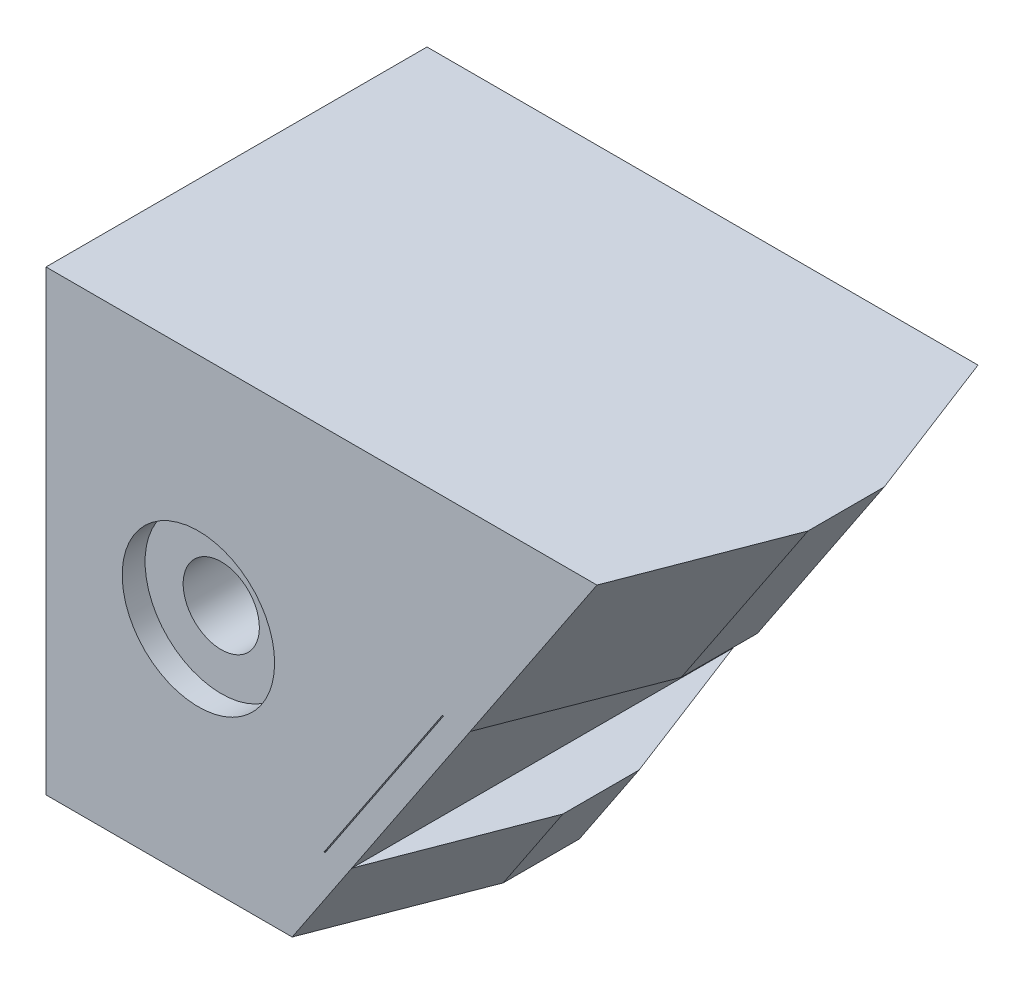
SolidWorks part; units mm, degrees
ref_plane "Front Plane" through (0, 0, 0) normal (0, 0, 1) x (1, 0, 0)
ref_plane "Top Plane" through (0, 0, 0) normal (0, 1, 0) x (1, 0, 0)
ref_plane "Right Plane" through (0, 0, 0) normal (1, 0, 0) x (0, 0, -1)
sketch "Sketch1" plane through (0, 0, 0) normal (0, 0, 1) x (1, 0, 0)
  line L0 (-77.1159, 75.2062) -> (-17.1159, 75.2062)
  line L1 (-17.1159, 75.2062) -> (-57.1159, 15.2062)
  line L2 (-57.1159, 15.2062) -> (-77.1159, 15.2062)
  line L3 (-77.1159, 15.2062) -> (-77.1159, 75.2062)
  line L4 (-17.1159, 75.2062) -> (2.8841, 75.2062)
  line L5 (2.8841, 75.2062) -> (-13.7569, 50.2447)
  line L6 (-13.7569, 50.2447) -> (-25.1095, 50.2447)
  line L7 (-25.1095, 50.2447) -> (-40.6411, 26.9473)
  line L8 (-29.2885, 26.9473) -> (-37.1159, 15.2062)
  line L9 (-40.6411, 26.9473) -> (-29.2885, 26.9473)
  line L10 (-37.1159, 15.2062) -> (-57.1159, 15.2062)
  dimension "D1" = 28
  dimension "D2" = 30
  dimension "D3" = 60
  dimension "D4" = 60
  dimension "D5" = 20
  dimension "D6" = 20
extrude "Boss-Extrude4" add sketch "Sketch1" against normal blind 50 contours L10 L8 L9 L7 L6 L5 L4 L1 | L3 L2 L1 L0 region at (-55.4492, 50.2062, 0) region at (-7.1159, 74.3577, 0)
hole_wizard "CBORE for #00 Binding Head Machine Screw2" positions "Sketch10" profile "Sketch9" counterbore size "#00" standard "ANSI Inch" end condition through all
sketch "Sketch10" plane through (0, 0, 0) normal (0, 0, 1) x (1, 0, 0)
  line L0 (-77.1159, 75.2062) -> (2.8841, 75.2062) construction
  line L1 (-77.1159, 15.2062) -> (-77.1159, 75.2062) construction
  point P0 (-57.1159, 45.2062)
  dimension "D1" = 30
  dimension "D2" = 20
sketch "Sketch9" plane through (-57.1159, 45.2062, 0) normal (1, 0, 0) x (0, -1, 0)
  line L0 (0, 0) -> (0, 50)
  line L1 (0, 50) -> (5, 50)
  line L3 (5, 50) -> (5, 3)
  line L4 (5, 3) -> (10, 3)
  line L5 (10, 3) -> (10, 0)
  line L7 (10, 0) -> (0, 0)
  line L11 (0, -6.35) -> (0, 107.95) construction
  dimension "Thru Hole Dia." = 10
  dimension "Thru Hole Depth" = 50
  dimension "C'Bore Dia." = 20
  dimension "C'Bore Depth" = 3
ref_plane "Plane4" through (3.4254, 5.1381, 0) normal (0.5547, 0.8321, 0) x (0, 0, 1)
sketch "Sketch13" plane through (3.4254, 5.1381, 0) normal (0.5547, 0.8321, 0) x (0, 0, 1)
  line L1 (-50, -39.3172) -> (0, -39.3172) construction
  line L2 (-20, -39.3172) -> (-30, -39.3172)
  line L3 (-50, -45.7203) -> (-50, -48.6358)
  line L4 (-50, -45.7203) -> (-30, -39.3172)
  line L6 (-50, -45.7203) -> (0, -45.7203)
  line L7 (-20, -39.3172) -> (0, -45.7203)
  line L8 (-20, -39.3172) -> (-30, -39.3172)
  line L9 (-50, -48.6358) -> (0, -48.6358)
  line L10 (0, -48.6358) -> (0, -45.7203)
  line L11 (-50, -45.7203) -> (-50, -39.3172)
  line L12 (-50, -39.3172) -> (-30, -39.3172)
  line L14 (-20, -39.3172) -> (0, -39.3172)
  line L15 (0, -39.3172) -> (0, -45.7203)
  dimension "D1" = 10
  dimension "D2" = 21
  dimension "D3" = 21
  dimension "D4" = 20
  dimension "D5" = 50
extrude "Boss-Extrude5" add sketch "Sketch13" along normal up to body and the other way up to body separate body contours L9 L10 L6 L3 region at (-35.8291, 31.3078, -25)
extrude "Cut-Extrude4" cut sketch "Sketch13<5>" against normal up to next and the other way up to next contours L12 L11 L4 | L15 L14 L7 region at (-31.0644, 28.1313, -6.6667) region at (-31.0644, 28.1313, -43.3333)
sketch "Sketch13<5>" plane through (3.4254, 5.1381, 0) normal (0.5547, 0.8321, 0) x (0, 0, 1) same geometry as "Sketch13"
